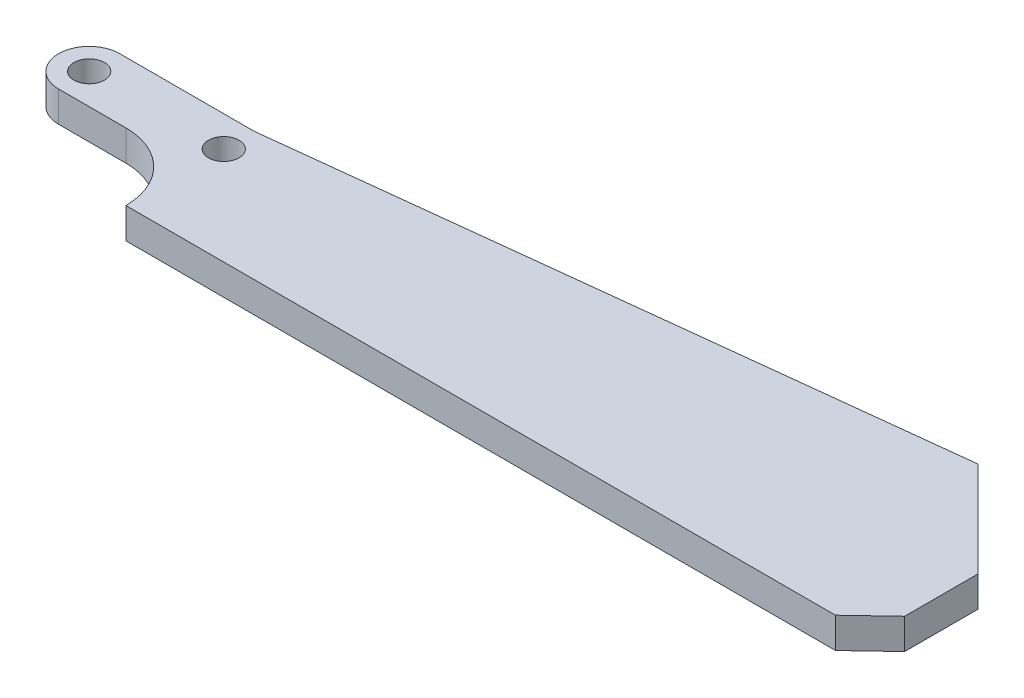
SolidWorks part; units mm, degrees
ref_plane "前视基准面" through (0, 0, 0) normal (0, 0, 1) x (1, 0, 0)
ref_plane "上视基准面" through (0, 0, 0) normal (0, 1, 0) x (1, 0, 0)
ref_plane "右视基准面" through (0, 0, 0) normal (1, 0, 0) x (0, 0, -1)
other "Configuration Table"
sketch "草图1" plane through (0, 0, 0) normal (0, 1, 0) x (1, 0, 0)
  line L0 (0, 0) -> (0, 5) construction
  line L1 (0, 5) -> (0, -5) construction
  line L2 (0, -5) -> (11, -5) construction
  line L3 (11, -5) -> (-11, -5) construction
  line L4 (-11, -5) -> (-11, 0) construction
  line L5 (-11, 0) -> (11, 0) construction
  line L6 (11, -5) -> (-11, -5)
  line L7 (-11, 5) -> (11, 5)
  line L8 (11, -5) -> (11, -16)
  line L9 (11, -16) -> (19, -16)
  line L10 (19, -16) -> (119, -16)
  line L11 (119, -16) -> (127, -16)
  line L12 (127, -16) -> (127, -10.5) construction
  line L13 (127, -16) -> (132.8095, -10.5)
  line L14 (132.8095, -10.5) -> (132.8095, 1.5)
  line L15 (132.8095, 1.5) -> (132.8095, 11.5) construction
  line L16 (132.8095, 11.5) -> (122.8095, 11.5) construction
  line L17 (132.8095, 1.5) -> (120.0816, 14.2279)
  line L18 (120.0816, 14.2279) -> (117.2531, 17.0563)
  line L19 (117.2531, 17.0563) -> (11, 5)
  arc A0 (-11, -5) -> (-11, 5) centre (-11, 0) cw
  circle A1 centre (-11, 0) radius 2.5
  circle A2 centre (11, 0) radius 2.5
  dimension "D7" = 22
  dimension "D12" = 12
  dimension "D17" = 5
  dimension "D18" = 5
  dimension "D1" = 5
  dimension "D2" = 10
  dimension "D3" = 11
  dimension "D4" = 22
  dimension "D5" = 5
  dimension "D6" = 22
  dimension "D8" = 11
  dimension "D9" = 8
  dimension "D10" = 100
  dimension "D11" = 8
  dimension "D13" = 10
  dimension "D14" = 10
  dimension "D15" = 18
  dimension "D16" = 4
extrude "凸台-拉伸1" add sketch "草图1" along normal blind 5
fillet "圆角2" radius 11 1 edges at (11, 2.5, 5)
fillet "圆角3" radius 11 1 edges at (11, 2.5, -5)
